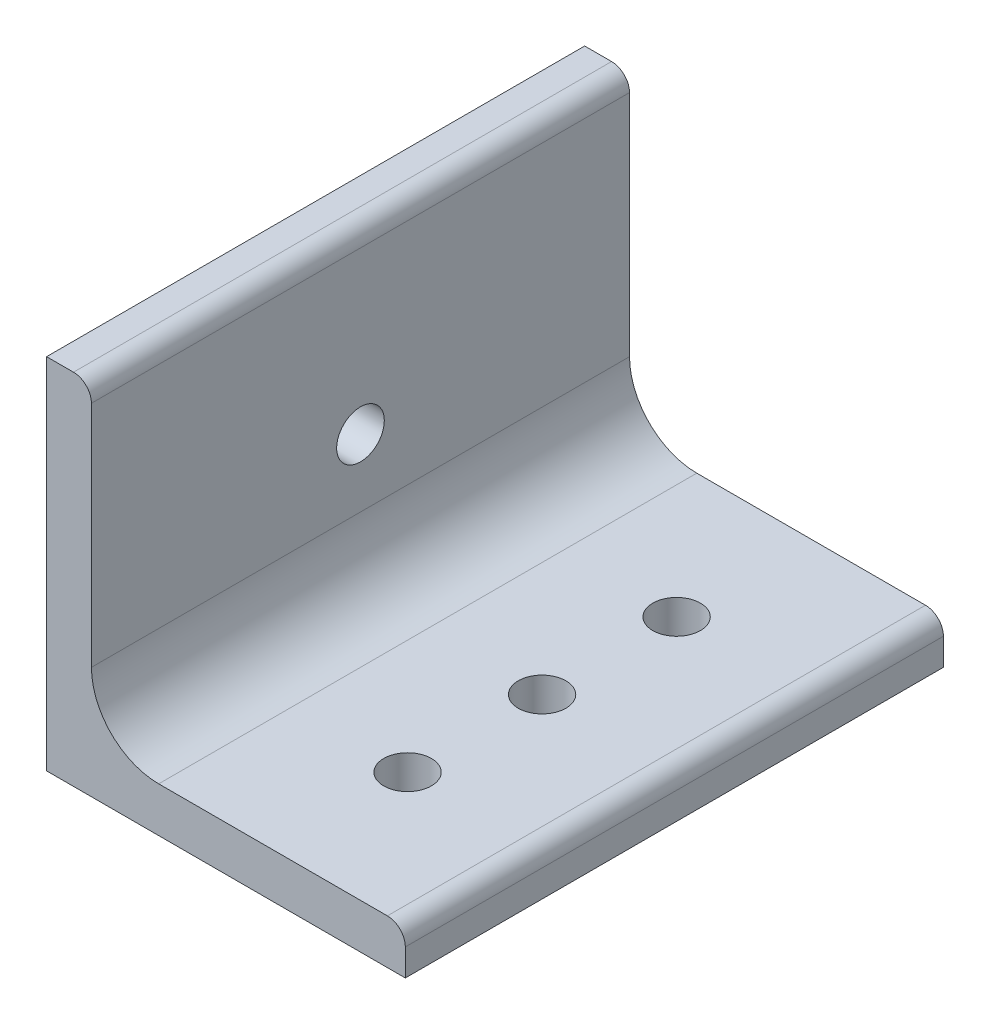
SolidWorks part; units mm, degrees
ref_plane "Front" through (0, 0, 0) normal (0, 0, 1) x (1, 0, 0)
ref_plane "Top" through (0, 0, 0) normal (0, 1, 0) x (1, 0, 0)
ref_plane "Right" through (0, 0, 0) normal (1, 0, 0) x (0, 0, -1)
sketch "Sketch1" plane through (0, 0, 0) normal (0, 0, 1) x (1, 0, 0)
  line L0 (0, 0) -> (0, 88.9)
  line L1 (0, 88.9) -> (-12.7, 88.9)
  line L2 (-12.7, 88.9) -> (-12.7, -12.7)
  line L3 (-12.7, -12.7) -> (88.9, -12.7)
  line L4 (88.9, -12.7) -> (88.9, 0)
  line L5 (88.9, 0) -> (0, 0)
  dimension "Outside Height" = 101.6
  dimension "Outside Width" = 101.6
  dimension "Wall Thickness" = 12.7
  dimension "Inside Width" = 88.9
  dimension "Inside Height" = 88.9
sketch "Sketch2" plane through (0, 0, 0) normal (1, 0, 0) x (0, 0, -1)
  line L0 (-76.2, 0) -> (76.2, 0) construction
  line L1 (76.2, -12.7) -> (-76.2, -12.7) construction
  point P2 (0, 0)
  point P3 (0, -12.7)
  point P5 (76.2, 0)
  point P6 (35.56, -12.7)
  point P9 (0, -12.7)
  point P10 (-76.2, -12.7)
  point P11 (76.2, -12.7)
  point P12 (-76.2, 0)
  point P14 (-35.56, -12.7)
  dimension "Length" = 152.4
  dimension "D1" = 111.76
  dimension "D2" = 111.76
sketch "Sketch3" plane through (0, 0, 0) normal (0, 0, 1) x (1, 0, 0)
  line L0 (0, 0) -> (0, 88.9) construction
  line L1 (0, 88.9) -> (-12.7, 88.9) construction
  line L2 (-12.7, 88.9) -> (-12.7, -12.7) construction
  line L3 (-12.7, -12.7) -> (88.9, -12.7) construction
  line L4 (88.9, -12.7) -> (88.9, 0) construction
  line L5 (88.9, 0) -> (0, 0) construction
  line L6 (0, 19.05) -> (0, 83.82)
  line L7 (-5.08, 88.9) -> (-12.7, 88.9)
  line L8 (-12.7, 88.9) -> (-12.7, -12.7)
  line L9 (-12.7, -12.7) -> (88.9, -12.7)
  line L10 (88.9, -12.7) -> (88.9, -5.08)
  line L11 (83.82, 0) -> (19.05, 0)
  arc A0 (0, 19.05) -> (19.05, 0) centre (19.05, 19.05) ccw
  arc A1 (88.9, -5.08) -> (83.82, 0) centre (83.82, -5.08) ccw
  arc A2 (0, 83.82) -> (-5.08, 88.9) centre (-5.08, 83.82) ccw
  dimension "D1" = 5.08
  dimension "D2" = 19.05
extrude "Boss-Extrude1" add sketch "Sketch3" along normal up to vertex (76.2 mm away) and the other way up to vertex (76.2 mm away) up to point (0, 0, 76.2) other way up to point (0, 0, -76.2)
sketch "Sketch4" plane through (0, 0, 0) normal (1, 0, 0) x (0, 0, -1)
  line L0 (-76.2, -12.7) -> (76.2, -12.7) construction
  line L1 (0, 55.88) -> (0, -55.88) construction
  point P0 (0, 38.1)
  point P3 (7.3006, 38.1)
  dimension "D1" = 50.8
hole_wizard "M12 Clearance Hole1" positions "Sketch4" profile "Sketch5" hole size "M12" standard "ANSI Metric" end condition through all
sketch "Sketch5" plane through (0, 38.1, 0) normal (0, 1, 0) x (0, 0, -1)
  line L0 (0, 0) -> (0, 12.7)
  line L1 (0, 12.7) -> (6.75, 12.7)
  line L2 (6.75, 12.7) -> (6.75, 0)
  line L5 (6.75, 0) -> (0, 0)
  line L11 (0, -6.35) -> (0, 107.95) construction
  dimension "Thru Hole Dia." = 13.5
  dimension "Thru Hole Depth" = 12.7
sketch "Sketch6" plane through (0, 0, 0) normal (0, 1, 0) x (1, 0, 0)
  line L0 (83.82, 76.2) -> (19.05, 76.2) construction
  line L1 (51.435, 76.2) -> (51.435, 38.1) construction
  line L2 (51.435, 38.1) -> (51.435, 0) construction
  line L3 (51.435, 0) -> (51.435, -38.1) construction
  line L4 (51.435, -38.1) -> (51.435, -76.2) construction
  line L5 (83.82, -76.2) -> (19.05, -76.2) construction
  point P12 (51.435, 38.1)
  point P13 (51.435, 0)
  point P14 (51.435, -38.1)
hole_wizard "1/2 Clearance Hole1" positions "Sketch6" profile "Sketch7" hole size "1/2" standard "ANSI Inch" end condition through all
sketch "Sketch7" plane through (51.435, 0, 38.1) normal (1, 0, 0) x (0, 0, 1)
  line L0 (0, 0) -> (0, 12.7)
  line L1 (0, 12.7) -> (6.7462, 12.7)
  line L2 (6.7462, 12.7) -> (6.7462, 0)
  line L5 (6.7462, 0) -> (0, 0)
  line L11 (0, -6.35) -> (0, 107.95) construction
  dimension "Thru Hole Dia." = 13.4925
  dimension "Thru Hole Depth" = 12.7
equation "\"D1@Sketch3\"=\"Wall Thickness@Sketch1\"*0.4"
equation "\"D2@Sketch3\"=\"Wall Thickness@Sketch1\"*1.5"
equation "\"D1@Sketch2\" = \"Outside Width@Sketch1\" * 1.1"
equation "\"D2@Sketch2\"=\"D1@Sketch2\""
